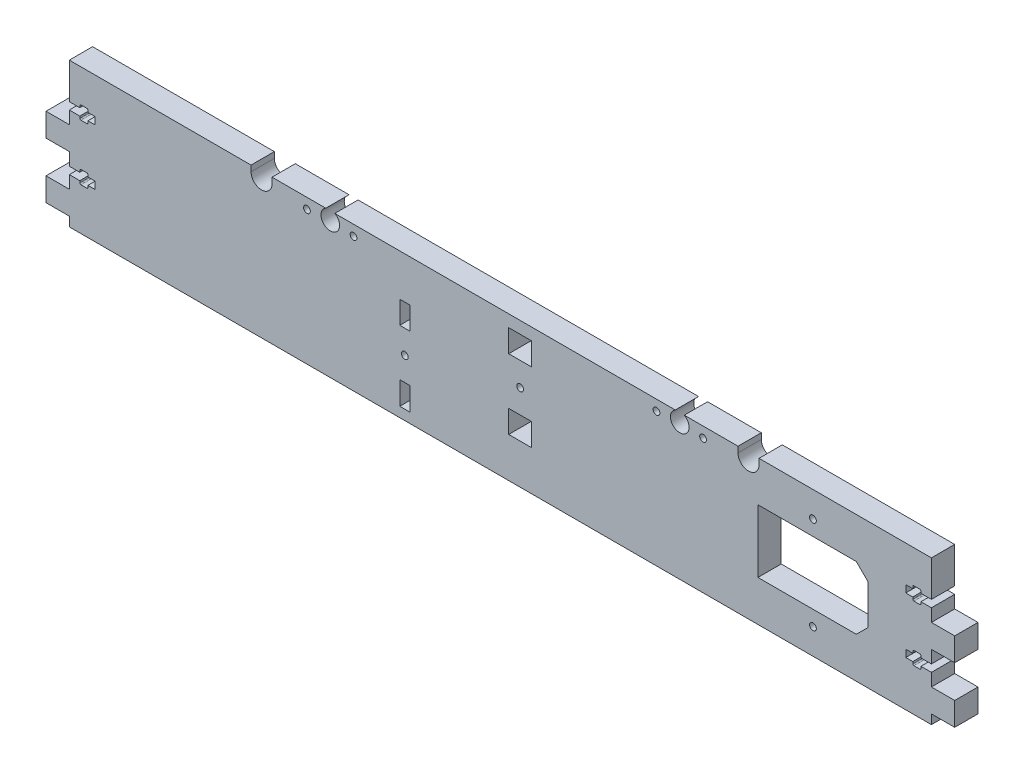
SolidWorks part; units mm, degrees
ref_plane "Front Plane" through (0, 0, 0) normal (0, 0, 1) x (1, 0, 0)
ref_plane "Top Plane" through (0, 0, 0) normal (0, 1, 0) x (1, 0, 0)
ref_plane "Right Plane" through (0, 0, 0) normal (1, 0, 0) x (0, 0, -1)
sketch "Sketch1" plane through (0, 0, 0) normal (0, 0, 1) x (1, 0, 0)
  line L0 (0, 0) -> (-185, 0)
  line L1 (-185, 0) -> (-185, -62) construction
  line L2 (0, -62) -> (-185, -62)
  line L3 (-185, -62) -> (-185, -58)
  line L4 (-185, -58) -> (-195, -58)
  line L5 (-195, -58) -> (-195, -48)
  line L6 (-195, -48) -> (-185, -48)
  line L7 (-185, -48) -> (-185, -34)
  line L8 (-185, -34) -> (-195, -34)
  line L9 (-195, -34) -> (-195, -24)
  line L10 (-195, -24) -> (-185, -24)
  line L11 (0, -62) -> (0, 0)
  line L12 (-185, -24) -> (-185, 0)
  line L13 (-195, -58) -> (-195, -24) construction
  line L14 (-195, -29) -> (-185, -29) construction
  line L15 (-195, -53) -> (-185, -53) construction
  dimension "D1" = 185
  dimension "D2" = 10
  dimension "D3" = 10
  dimension "D4" = 10
  dimension "D5" = 24
  dimension "D6" = 29
  dimension "D7" = 62
extrude "MainBody" add sketch "Sketch1" along normal blind 10
sketch "Sketch3" plane through (0, 0, 10) normal (0, 0, 1) x (1, 0, 0)
  line L0 (-185, -17) -> (-174, -17) construction
  line L1 (-185, 0) -> (-185, -24) construction
  line L2 (-185, -18.55) -> (-180.5, -18.55)
  line L3 (-180.5, -18.55) -> (-180.5, -19.35)
  line L4 (-180, -19.85) -> (-177.5, -19.85)
  line L5 (-177, -19.35) -> (-177, -18.55)
  line L6 (-177, -18.55) -> (-174, -18.55)
  line L7 (-174, -18.55) -> (-174, -15.45)
  line L8 (-180.5, -18.55) -> (-177, -18.55) construction
  line L9 (-195, -24) -> (-195, -34) construction
  line L10 (-180.5, -15.45) -> (-177, -15.45) construction
  line L11 (-177, -15.45) -> (-174, -15.45)
  line L12 (-177, -14.65) -> (-177, -15.45)
  line L13 (-180, -14.15) -> (-177.5, -14.15)
  line L14 (-180.5, -15.45) -> (-180.5, -14.65)
  line L15 (-185, -15.45) -> (-180.5, -15.45)
  line L16 (-185, -18.55) -> (-185, -15.45)
  line L17 (-185, -24) -> (-185, -34) construction
  line L19 (-195, -24) -> (-195, -34) construction
  line L20 (-195, -29) -> (-185, -29) construction
  line L21 (-180.5, -42.55) -> (-177, -42.55) construction
  line L22 (-180.5, -39.45) -> (-177, -39.45) construction
  line L23 (-185, -41) -> (-174, -41) construction
  line L24 (-185, -39.45) -> (-185, -42.55)
  line L25 (-185, -42.55) -> (-180.5, -42.55)
  line L26 (-180.5, -42.55) -> (-180.5, -43.35)
  line L27 (-180, -43.85) -> (-177.5, -43.85)
  line L28 (-177, -43.35) -> (-177, -42.55)
  line L29 (-177, -42.55) -> (-174, -42.55)
  line L30 (-174, -39.45) -> (-174, -42.55)
  line L31 (-177, -39.45) -> (-174, -39.45)
  line L32 (-177, -38.65) -> (-177, -39.45)
  line L33 (-180, -38.15) -> (-177.5, -38.15)
  line L34 (-180.5, -39.45) -> (-180.5, -38.65)
  line L35 (-185, -39.45) -> (-180.5, -39.45)
  line L36 (-180.5, -15.45) -> (-177, -15.45) construction
  arc A0 (-177.5, -19.85) -> (-177, -19.35) centre (-177.5, -19.35) ccw
  arc A1 (-180.5, -19.35) -> (-180, -19.85) centre (-180, -19.35) ccw
  arc A2 (-180.5, -14.65) -> (-180, -14.15) centre (-180, -14.65) cw
  arc A3 (-177.5, -14.15) -> (-177, -14.65) centre (-177.5, -14.65) cw
  arc A4 (-177.5, -43.85) -> (-177, -43.35) centre (-177.5, -43.35) ccw
  arc A5 (-180.5, -43.35) -> (-180, -43.85) centre (-180, -43.35) ccw
  arc A6 (-180.5, -38.65) -> (-180, -38.15) centre (-180, -38.65) cw
  arc A7 (-177.5, -38.15) -> (-177, -38.65) centre (-177.5, -38.65) cw
  point P6 (-195, -29)
  point P15 (-177, -19.85)
  point P18 (-180.5, -19.85)
  point P29 (-180.5, -14.15)
  point P30 (-177, -14.15)
  point P62 (-177, -43.85)
  point P63 (-180.5, -43.85)
  point P64 (-180.5, -38.15)
  point P65 (-177, -38.15)
  dimension "D2" = 8
  dimension "D7" = 0.5
  dimension "D1" = 11
  dimension "D3" = 1.55
  dimension "D4" = 2.85
  dimension "D5" = 12
  dimension "D6" = 3.5
extrude "ScrewCutouts" cut sketch "Sketch3" against normal through all
mirror "Mirror1" about plane through (0, 0, 0) normal (1, 0, 0) of "ScrewCutouts", "MainBody"
sketch "Sketch2" plane through (0, 0, 10) normal (0, 0, 1) x (1, 0, 0)
  line L0 (0, 0) -> (0, -62) construction
  line L1 (-185, -62) -> (185, -62) construction
  line L2 (2, 0) -> (2, -62) construction
  line L3 (185, 0) -> (-185, 0) construction
  line L4 (-63, -4.5) -> (-83, -4.5) construction
  line L5 (-73, -7.5) -> (-73, 0.5) construction
  line L6 (77, -7.5) -> (77, 0.5) construction
  line L7 (67, -4.5) -> (87, -4.5) construction
  circle A0 centre (-73, -3.5) radius 4
  circle A1 centre (-83, -4.5) radius 1.45
  circle A2 centre (-63, -4.5) radius 1.45
  circle A3 centre (67, -4.5) radius 1.45
  circle A4 centre (87, -4.5) radius 1.45
  circle A5 centre (77, -3.5) radius 4
  dimension "D1" = 2.9
  dimension "D2" = 8
  dimension "D4" = 3.5
  dimension "D5" = 75
  dimension "D6" = 2
  dimension "D3" = 10
  dimension "D7" = 1
extrude "RodCutouts" cut sketch "Sketch2" against normal through all
sketch "Sketch4" plane through (0, 0, 10) normal (0, 0, 1) x (1, 0, 0)
  line L0 (77, -3.5) -> (-73, -3.5) construction
  line L1 (2, -3.5) -> (2, -62) construction
  line L2 (-185, -62) -> (185, -62) construction
  line L3 (8.5, -44.85) -> (8.5, -5.15) construction
  line L4 (75.0635, 0) -> (-71.0635, 0) construction
  line L5 (8.5, -10) -> (8.5, -40) construction
  line L6 (3.575, -5.15) -> (13.425, -5.15)
  line L7 (3.575, -5.15) -> (3.575, -14.85)
  line L8 (3.575, -14.85) -> (13.425, -14.85)
  line L9 (13.425, -5.15) -> (13.425, -14.85)
  line L10 (3.575, -5.15) -> (13.425, -14.85) construction
  line L11 (3.575, -14.85) -> (13.425, -5.15) construction
  line L12 (3.575, -35.15) -> (13.425, -35.15)
  line L13 (3.575, -35.15) -> (3.575, -44.85)
  line L14 (3.575, -44.85) -> (13.425, -44.85)
  line L15 (13.425, -35.15) -> (13.425, -44.85)
  line L16 (3.575, -35.15) -> (13.425, -44.85) construction
  line L17 (3.575, -44.85) -> (13.425, -35.15) construction
  circle A0 centre (8.5, -25) radius 1.45
  point P12 (8.5, -10)
  point P17 (8.5, -40)
  dimension "D8" = 2.9
  dimension "D1" = 9.85
  dimension "D2" = 9.7
  dimension "D3" = 9.85
  dimension "D4" = 9.7
  dimension "D5" = 30
  dimension "D6" = 10
  dimension "D7" = 6.5
extrude "Cut-Extrude3" cut sketch "Sketch4" against normal through all
sketch "Sketch5" plane through (0, 0, 10) normal (0, 0, 1) x (1, 0, 0)
  line L0 (-41, 0) -> (-41, -62) construction
  line L1 (-74.9365, 0) -> (-185, 0) construction
  line L2 (-185, -62) -> (185, -62) construction
  line L3 (-43.175, -27.65) -> (-43.175, -47.85) construction
  line L4 (-43.175, -17.95) -> (-38.825, -17.95)
  line L5 (-43.175, -17.95) -> (-43.175, -27.65)
  line L6 (-43.175, -27.65) -> (-38.825, -27.65)
  line L7 (-38.825, -17.95) -> (-38.825, -27.65)
  line L8 (-43.175, -17.95) -> (-38.825, -27.65) construction
  line L9 (-43.175, -27.65) -> (-38.825, -17.95) construction
  line L10 (-43.175, -47.85) -> (-38.825, -47.85)
  line L11 (-43.175, -47.85) -> (-43.175, -57.75)
  line L12 (-43.175, -57.75) -> (-38.825, -57.75)
  line L13 (-38.825, -47.85) -> (-38.825, -57.75)
  line L14 (-43.175, -47.85) -> (-38.825, -57.75) construction
  line L15 (-43.175, -57.75) -> (-38.825, -47.85) construction
  line L16 (-38.825, -47.85) -> (-38.825, -27.65) construction
  line L17 (-43.175, -37.75) -> (-38.825, -37.75) construction
  line L18 (-73, -3.5) -> (77, -3.5) construction
  line L19 (2, -3.5) -> (2, -62) construction
  line L20 (2, -32.75) -> (-195, -32.75) construction
  line L21 (-195, -24) -> (-195, -34) construction
  line L22 (-34.625, 8.9944) -> (-34.625, 5) construction
  line L23 (75.0635, 0) -> (-71.0635, 0) construction
  line L24 (-31.425, 8.9944) -> (-31.425, 5)
  line L25 (-37.825, 8.9944) -> (-37.825, 5)
  circle A0 centre (-41, -37.75) radius 1.45
  arc A1 (-31.425, 8.9944) -> (-37.825, 8.9944) centre (-34.625, 8.9944) ccw
  arc A2 (-37.825, 5) -> (-31.425, 5) centre (-34.625, 5) ccw
  point P6 (-41, -22.8)
  point P11 (-41, -52.8)
  point P34 (-34.625, 6.9972)
  dimension "D4" = 9.7
  dimension "D5" = 30
  dimension "D6" = 2.9
  dimension "D9" = 3.2
  dimension "D1" = 4.35
  dimension "D2" = 0
  dimension "D3" = 9.9
  dimension "D7" = 43
  dimension "D8" = 5
  dimension "D10" = 5
  dimension "D11" = 1
extrude "EndstopHolder" cut sketch "Sketch5" against normal through all
sketch "Sketch6" plane through (0, 0, 10) normal (0, 0, 1) x (1, 0, 0)
  line L0 (-43.175, -47.85) -> (-43.175, -27.65) construction
  line L1 (-42.35, -47.85) -> (-30.825, -47.85) construction
  line L3 (-30.825, -53.85) -> (-30.825, -41.85) construction
  line L4 (-32.825, -53.85) -> (-32.825, -41.85)
  line L5 (-28.825, -53.85) -> (-28.825, -41.85)
  line L6 (-38.825, -47.85) -> (-43.175, -47.85) construction
  line L7 (-38.825, -57.75) -> (-38.825, -47.85) construction
  arc A0 (-32.825, -53.85) -> (-28.825, -53.85) centre (-30.825, -53.85) ccw
  arc A1 (-28.825, -41.85) -> (-32.825, -41.85) centre (-30.825, -41.85) ccw
  point P10 (-30.825, -47.85)
  dimension "D1" = 2
  dimension "D2" = 12
  dimension "D3" = 8
  dimension "D4" = 0
extrude "EndstopWires" [suppressed] cut sketch "Sketch6" against normal through all
sketch "Sketch7" plane through (0, 0, 10) normal (0, 0, 1) x (1, 0, 0)
  line L0 (-73, -3.5) -> (77, -3.5) construction
  line L1 (2, -3.5) -> (2, -62) construction
  line L3 (-102.5, 0) -> (-102.5, -2.5) construction
  line L4 (-74.9365, 0) -> (-185, 0) construction
  line L5 (-98, 0) -> (-98, -2.5)
  line L6 (-107, 0) -> (-107, -2.5)
  line L7 (106.5, 0) -> (106.5, -2.5) construction
  line L8 (102, 0) -> (102, -2.5)
  line L9 (111, 0) -> (111, -2.5)
  line L10 (-185, -62) -> (185, -62) construction
  arc A0 (-98, 0) -> (-107, 0) centre (-102.5, 0) ccw
  arc A1 (-107, -2.5) -> (-98, -2.5) centre (-102.5, -2.5) ccw
  arc A2 (102, 0) -> (111, 0) centre (106.5, 0) cw
  arc A3 (111, -2.5) -> (102, -2.5) centre (106.5, -2.5) cw
  point P12 (-102.5, -1.25)
  point P19 (106.5, -1.25)
  dimension "D3" = 4.5
  dimension "D1" = 2.5
  dimension "D2" = 104.5
extrude "Cut-Extrude4" cut sketch "Sketch7" against normal through all
ref_plane "Plane1" through (0, -31, 0) normal (0, 1, 0) x (1, 0, 0)
sketch "Sketch8" plane through (0, 0, 10) normal (0, 0, 1) x (1, 0, 0)
  line L0 (133.7748, 0) -> (133.7748, -62) construction
  line L1 (185, 0) -> (111, 0) construction
  line L2 (-185, -62) -> (185, -62) construction
  line L3 (132.2469, -17.485) -> (110.5361, -17.485) construction
  line L4 (151.9576, -17.485) -> (112.5361, -17.485) construction
  line L5 (110.5361, -17.485) -> (110.5361, -44.515)
  line L6 (110.5361, -19.485) -> (110.5361, -42.515) construction
  line L7 (112.5361, -44.515) -> (151.9576, -44.515) construction
  line L8 (110.5361, -44.515) -> (152.7861, -44.515)
  line L9 (152.7861, -44.515) -> (157.7861, -39.515)
  line L10 (157.7861, -39.515) -> (157.7861, -22.485)
  line L11 (157.7861, -22.485) -> (152.7861, -17.485)
  line L12 (152.7861, -17.485) -> (110.5361, -17.485)
  line L13 (157.7861, -38.6866) -> (157.7861, -23.3134) construction
  line L14 (157.2003, -21.8992) -> (153.3719, -18.0708) construction
  line L15 (153.3719, -43.9292) -> (157.2003, -40.1008) construction
extrude "Cut-Extrude5" cut sketch "Sketch8" against normal through all
sketch "Sketch9" plane through (0, 0, 0) normal (0, 0, -1) x (-1, 0, 0)
  line L0 (-105.0611, -31) -> (-163.2611, -31) construction
  line L1 (-105.0611, -43.5977) -> (-105.0611, -18.4023) construction
  line L2 (-163.2611, -18.4023) -> (-163.2611, -43.5977) construction
  circle A0 centre (-134.1611, -11) radius 1.45
  circle A1 centre (-134.1611, -11) radius 1.6 construction
  circle A2 centre (-134.1611, -51) radius 1.45
  dimension "D1" = 2.9
extrude "Cut-Extrude6" cut sketch "Sketch9" against normal through all
equation "\"Y-ROD-SPACING\"=75"
equation "\"D5@Sketch2\"=\"Y-ROD-SPACING\""
equation "\"Y-BED-OFFSET\"=2"
equation "\"D6@Sketch2\"=\"Y-BED-OFFSET\""
equation "\"T-SLOT-NUT-FILLET-RADIUS\"=0.5"
equation "\"D7@Sketch3\"=\"T-SLOT-NUT-FILLET-RADIUS\""
equation "\"T-SLOT-SCREW-SHAFT-RADIUS\"=1.55"
equation "\"D3@Sketch3\"=\"T-SLOT-SCREW-SHAFT-RADIUS\""
equation "\"T-SLOT-SCREW-SHAFT-CUTOUT-LENGTH\"=11"
equation "\"D1@Sketch3\"=\"T-SLOT-SCREW-SHAFT-CUTOUT-LENGTH\""
equation "\"T-SLOT-NUT-DEPTH\"=3.5"
equation "\"D6@Sketch3\"=\"T-SLOT-NUT-DEPTH\""
equation "\"T-SLOT-NUT-WIDTH\"=2.85"
equation "\"D4@Sketch3\"=\"T-SLOT-NUT-WIDTH\""
equation "\"T-SLOT-NUT-END-DISTANCE\"=8"
equation "\"D2@Sketch3\"=\"T-SLOT-NUT-END-DISTANCE\""
equation "\"ACRYLIC-TAB-CUTOUT-SIZE\"=\"ACRYLIC-THICKNESS\"+\"ACRYLIC-TAB-TOLERANCE\"*2"
equation "\"D1@Sketch4\"=\"ACRYLIC-THICKNESS\"-\"KERF\"*2"
equation "\"D2@Sketch4\"=\"ACRYLIC-TAB-WIDTH\"-\"KERF\"*4"
equation "\"D3@Sketch4\"=\"ACRYLIC-THICKNESS\"-\"KERF\"*2"
equation "\"D4@Sketch4\"=\"ACRYLIC-TAB-WIDTH\"-\"KERF\"*4"
equation "\"ACRYLIC-M3-HOLE\"=2.9"
equation "\"D8@Sketch4\"=\"ACRYLIC-M3-HOLE\""
equation "\"Y-BED-ROD-INSET\"=3.5"
equation "\"D1@Sketch2\"=\"ACRYLIC-M3-HOLE\""
equation "\"D4@Sketch2\"=\"Y-BED-ROD-INSET\""
equation "\"SMOOTHROD-CAP-SCREW-DISTANCE\"=20"
equation "\"D3@Sketch2\"=\"SMOOTHROD-CAP-SCREW-DISTANCE\"/2"
equation "\"ACRYLIC-TAB-WIDTH\"=\"ACRYLIC-THICKNESS\""
equation "\"FRAME-WIDTH-INNER\"=370"
equation "\"D2@Sketch1\"=\"ACRYLIC-TAB-WIDTH\""
equation "\"D3@Sketch1\"=\"ACRYLIC-TAB-WIDTH\""
equation "\"D4@Sketch1\"=\"ACRYLIC-TAB-WIDTH\""
equation "\"D1@Sketch1\"=\"FRAME-WIDTH-INNER\"/2"
equation "\"X-ROD-SPACING\"=45"
equation "\"Z-ROD-SPACING\"=17.5"
equation "\"ACRYLIC-THICKNESS\"=10"
equation "\"ACRYLIC-THICKNESS2\"=4.5"
equation "\"NEMA17-HOLE-SPACING\"=31"
equation "\"NEMA17-CENTRAL-CUTOUT\"=22.5"
equation "\"Z-BRACKET-REACH\"=57"
equation "\"TOP-BRACKET-SPACING\"=40"
equation "\"SMOOTHROD-X-LENGTH\"=350"
equation "\"SMOOTHROD-Y-LENGTH\"=350"
equation "\"SMOOTHROD-Z-LENGTH\"=350"
equation "\"SMOOTHROD-TIGHTENING-HEADROOM\"=.25"
equation "\"LEADSCREW-Z-LENGTH\"=300"
equation "\"SCREW-LENGTH-FRAME\"=\"ACRYLIC-THICKNESS\" + 10"
equation "\"SCREW-HEAD-RADIUS\"=6"
equation "\"PRINTED-X-SMOOTHROD-DIAMETER\"=8.8"
equation "\"PRINTED-X-SMOOTHROD-CUTOUT\"=10"
equation "\"PRINTED-X-BASE-HEIGHT\"=10"
equation "\"PRINTED-LM8UU-CUTOUT-SIZE\"=15.5"
equation "\"PRINTED-LM8UU-CUTOUT-LENGTH\"=24.5"
equation "\"PRINTED-X-IDLER-HEIGHT\"=16"
equation "\"PSU-MOUNTING-WIDTH\"=95"
equation "\"PSU-MOUNTING-HEIGHT\"=177"
equation "\"D1@MainBody\"=\"ACRYLIC-THICKNESS\""
equation "\"D1@Sketch5\"=\"ACRYLIC-THICKNESS2\"-\"KERF\"*2"
equation "\"D3@Sketch5\"=\"ACRYLIC-TAB-CUTOUT-SIZE\""
equation "\"D4@Sketch5\"=\"ACRYLIC-TAB-WIDTH\"-\"KERF\"*4"
equation "\"D6@Sketch5\"=\"ACRYLIC-M3-HOLE\""
equation "\"Y-BED-SCREW-SPACING\"=209"
equation "\"Y-BED-SCREW-CUTOUT-SLOT-HEIGHT\"=2.5"
equation "\"Z-ROD-INSET\"=13.5"
equation "\"Y-BELT-TO-ROD-DISTANCE\"=20"
equation "\"SPOOL-HOLDER-ROD-SPACING\"=150"
equation "\"D1@Sketch7\"=\"Y-BED-SCREW-CUTOUT-SLOT-HEIGHT\""
equation "\"D2@Sketch7\"=\"Y-BED-SCREW-SPACING\"/2"
equation "\"ACRYLIC-TAB-TOLERANCE\"=-.05"
equation "\"SCREW-LENGTH-MOTOR\"=\"ACRYLIC-THICKNESS\" + 5"
equation "\"SCREW-LENGTH-EXTRUDER\"=28"
equation "\"ACRYLIC-X-CARRIAGE-WIDTH\"=55"
equation "\"ACRYLIC-X-CARRIAGE-HEIGHT\"=75"
equation "\"ACRYLIC-X-CARRIAGE-LM8UU-CUTOUT-WIDTH\"=24.25"
equation "\"ACRYLIC-X-CARRIAGE-SCREW-SPACING-X\"=15"
equation "\"ACRYLIC-X-CARRIAGE-SCREW-SPACING-Y\"=33"
equation "\"ACRYLIC-X-CARRIAGE-CENTER-TAB-SPACING\"=14"
equation "\"ACRYLIC-X-CARRIAGE-EXTRUDER-OFFSET\"=26"
equation "\"ACRYLIC-X-CARRIAGE-EXTRUDER-ANGLE\"=90"
equation "\"ACRYLIC-X-CARRIAGE-EXTRUDER-SHELF-DEPTH\"=\"ACRYLIC-X-CARRIAGE-EXTRUDER-OFFSET\" + 28"
equation "\"ACRYLIC-X-CARRIAGE-EXTRUDER-BRACE-SPACING\"=23"
equation "\"ACRYLIC-X-CARRIAGE-EXTRUDER-BRACE-TAB-OFFSET\"=20"
equation "\"ACRYLIC-X-CARRIAGE-EXTRUDER-BRACE-HEIGHT\"=35"
equation "\"ACRYLIC-X-CARRIAGE-EXTRUDER-BRACE-SCREW-SPACING\"=22"
equation "\"PRINTED-M3-HOLE\"=3.5"
equation "\"ACRYLIC-X-CARRIAGE-LM8UU-CUTOUT-HEIGHT\"=11.0"
equation "\"ACRYLIC-X-CARRIAGE-DUAL-WIDTH-MULTIPLIER\"=1.65"
equation "\"ACRYLIC-X-CARRIAGE-DUAL-HOTEND-SPACING\"=42"
equation "\"ACRYLIC-X-CARRIAGE-DUAL-WIDTH\"=75"
equation "\"ACRYLIC-X-CARRIAGE-DUAL-HOTEND-SEPARATION\"=36"
equation "\"ACRYLIC-X-CARRIAGE-DUAL-MOUNT-PLATE-DEPTH\"=75"
equation "\"ACRYLIC-X-CARRIAGE-DUAL-MOUNT-BRACE-WIDTH\"=33"
equation "\"ACRYLIC-X-CARRIAGE-DUAL-MOUNT-SCREW-WIDTH\"=40"
equation "\"BLOWER-FAN-WIDTH\"=15"
equation "\"KERF\"=0.075"
equation "\"PRINTED-M3-NUT-AF\"=6.25"
equation "\"ACRYLIC-X-CARRIAGE-DUAL-FAN-OFFSET\"=52"
equation "\"ACRYLIC-X-CARRIAGE-DUAL-FAN-HEIGHT\"=20"
equation "\"D1@Sketch9\"=\"ACRYLIC-M3-HOLE\""
